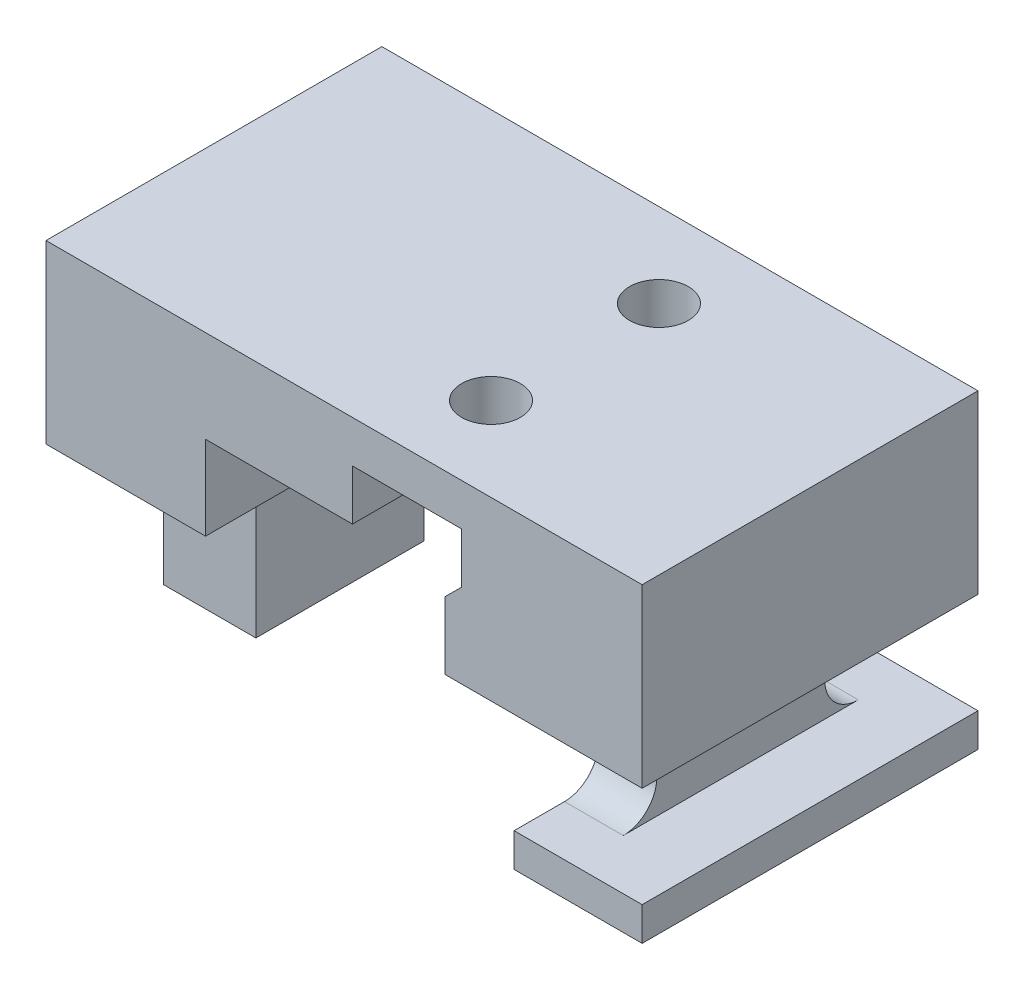
SolidWorks part; units mm, degrees
ref_plane "Front Plane" through (0, 0, 0) normal (0, 0, 1) x (1, 0, 0)
ref_plane "Top Plane" through (0, 0, 0) normal (0, 1, 0) x (1, 0, 0)
ref_plane "Right Plane" through (0, 0, 0) normal (1, 0, 0) x (0, 0, -1)
sketch "Sketch1" plane through (0, 0, 0) normal (0, 0, 1) x (1, 0, 0)
  line L0 (-16.75, 0) -> (16.75, 0)
  line L2 (2.75, 0) -> (2.75, -13.3769) construction
  line L5 (-16.75, 0) -> (-16.75, -10.5)
  line L7 (-11.25, -10.5) -> (-11.25, -5.5)
  line L8 (-11.25, -5.5) -> (0.5, -5.5)
  line L9 (0.5, -5.5) -> (0.5, -3.5)
  line L10 (0.5, -3.5) -> (5, -3.5)
  line L11 (5, -3.5) -> (5, -5.5)
  line L13 (5, -5.5) -> (5, -10.5)
  line L16 (5, -10.5) -> (16.75, -10.5)
  line L17 (16.75, 0) -> (16.75, -10.5)
  line L18 (-16.75, -10.5) -> (-11.25, -10.5)
  point P20 (2.75, -3.5)
  dimension "D1" = 33.5
  dimension "D2" = 5.5
  dimension "D3" = 11.75
  dimension "D4" = 19.5
  dimension "D5" = 5
  dimension "D7" = 2
extrude "Boss-Extrude1" add sketch "Sketch1" along normal blind 20 contours L18 L7 L8 L9 L10 L11 L13 L16 L17 L0 L5
sketch "Sketch2" plane through (0, -3.5, 0) normal (0, -1, 0) x (1, 0, 0)
  line L0 (2.75, 20) -> (2.75, -1.2502) construction
  line L1 (0.5, 20) -> (5, 20) construction
  line L2 (0.5, 0) -> (5, 0) construction
  circle A0 centre (2.75, 15) radius 1.75
  circle A1 centre (2.75, 5) radius 1.75
  dimension "D1" = 3.5
  dimension "D2" = 5
  dimension "D3" = 5
extrude "Cut-Extrude1" cut sketch "Sketch2" against normal up to surface (3.5 mm away) up to face at (0, 0, 10)
sketch "Sketch4" plane through (0, -10.5, 0) normal (0, -1, 0) x (1, 0, 0)
  line L0 (-16.75, 20) -> (-16.75, 0) construction
  line L1 (-16.75, 15) -> (-11.25, 15)
  line L2 (-16.75, 15) -> (-16.75, 5)
  line L3 (-16.75, 5) -> (-11.25, 5)
  line L4 (-11.25, 15) -> (-11.25, 5)
  line L6 (-11.25, 20) -> (-11.25, 0) construction
  dimension "D1" = 10
  dimension "D2" = 5
extrude "Boss-Extrude2" add sketch "Sketch4" along normal blind 8.75
sketch "Sketch5" plane through (0, -19.25, 0) normal (0, -1, 0) x (1, 0, 0)
  line L0 (-14, 5) -> (-14, 15) construction
  line L1 (-16.75, 5) -> (-11.25, 5) construction
  line L2 (-11.25, 15) -> (-16.75, 15) construction
  line L3 (-16.75, 10) -> (-11.25, 10) construction
  line L4 (-16.75, 15) -> (-16.75, 5) construction
  line L5 (-11.25, 20) -> (-11.25, 0) construction
  circle A0 centre (-14, 10) radius 0.875
  dimension "D1" = 1.75
extrude "Cut-Extrude2" cut sketch "Sketch5" against normal blind 10
ref_plane "Plane1" through (0, 0, 10) normal (0, 0, 1) x (1, 0, 0)
sketch "Sketch6" plane through (0, 0, 10) normal (0, 0, 1) x (1, 0, 0)
  line L0 (5, -10.5) -> (16.75, -10.5) construction
  line L1 (9.125, -10.5) -> (12.625, -10.5)
  line L2 (9.125, -10.5) -> (9.125, -16.5)
  line L3 (9.125, -16.5) -> (12.625, -16.5)
  line L4 (12.625, -10.5) -> (12.625, -16.5)
  line L5 (5, -3.5) -> (5, -10.5) construction
  dimension "D1" = 3.5
  dimension "D2" = 4.125
  dimension "D3" = 6
extrude "Boss-Extrude3" add sketch "Sketch6" against normal mid plane 10
fillet "Fillet1" radius 1 4 edges at (-14, -10.5, 5) (-14, -10.5, 15) (10.875, -10.5, 5) (10.875, -10.5, 15)
sketch "Sketch8" plane through (0, 0, 20) normal (0, 0, 1) x (1, 0, 0)
  line L0 (-11.25, -5.5) -> (0.5, -5.5) construction
  line L1 (-0.5, -2.5) -> (6, -2.5)
  line L2 (-0.5, -2.5) -> (-0.5, -5.5)
  line L3 (-0.5, -5.5) -> (6, -5.5)
  line L4 (6, -2.5) -> (6, -5.5)
  line L5 (0.5, -5.5) -> (0.5, -3.5) construction
  line L6 (5, -3.5) -> (5, -10.5) construction
  line L7 (0.5, -3.5) -> (5, -3.5) construction
  dimension "D1" = 1
  dimension "D2" = 1
  dimension "D3" = 1
extrude "Cut-Extrude3" cut sketch "Sketch8" against normal blind 30
chamfer "Chamfer1" distance 1 angle 45 1 edges at (5, -5.5, 10)
sketch "Sketch10" plane through (0, 0, 20) normal (0, 0, 1) x (1, 0, 0)
  line L0 (-16.75, 0) -> (16.75, 0) construction
  line L1 (-16.75, -10.5) -> (-18.75, -10.5)
  line L2 (-16.75, -10.5) -> (-16.75, 0)
  line L3 (-16.75, 0) -> (-18.75, 0)
  line L4 (-18.75, -10.5) -> (-18.75, 0)
  dimension "D1" = 2
extrude "Boss-Extrude5" add sketch "Sketch10" against normal up to surface (20 mm away) up to face at (-0.125, -5.8333, 0)
sketch "Sketch11" plane through (0, -10.5, 0) normal (0, -1, 0) x (1, 0, 0)
  line L0 (-11.25, 0) -> (-0.5, 0) construction
  line L1 (-11.25, 20) -> (-9.25, 20)
  line L2 (-11.25, 20) -> (-11.25, 0)
  line L3 (-11.25, 0) -> (-9.25, 0)
  line L4 (-9.25, 20) -> (-9.25, 0)
  dimension "D1" = 2
extrude "Boss-Extrude6" add sketch "Sketch11" against normal up to surface (5 mm away) up to face at (-5.875, -5.5, 10)
sketch "Sketch12" plane through (0, -16.5, 0) normal (0, -1, 0) x (1, 0, 0)
  line L5 (9.125, 0) -> (16.75, 0)
  line L6 (16.75, 20) -> (16.75, 0)
  line L7 (9.125, 20) -> (16.75, 20)
  line L8 (9.125, 20) -> (9.125, 0)
  line L9 (16.75, 20) -> (16.75, 0) construction
  line L10 (5, 0) -> (16.75, 0) construction
  line L11 (5, 20) -> (16.75, 20) construction
extrude "Boss-Extrude7" add sketch "Sketch12" along normal blind 2
fillet "Fillet2" radius 2 2 edges at (10.875, -16.5, 15) (10.875, -16.5, 5)
